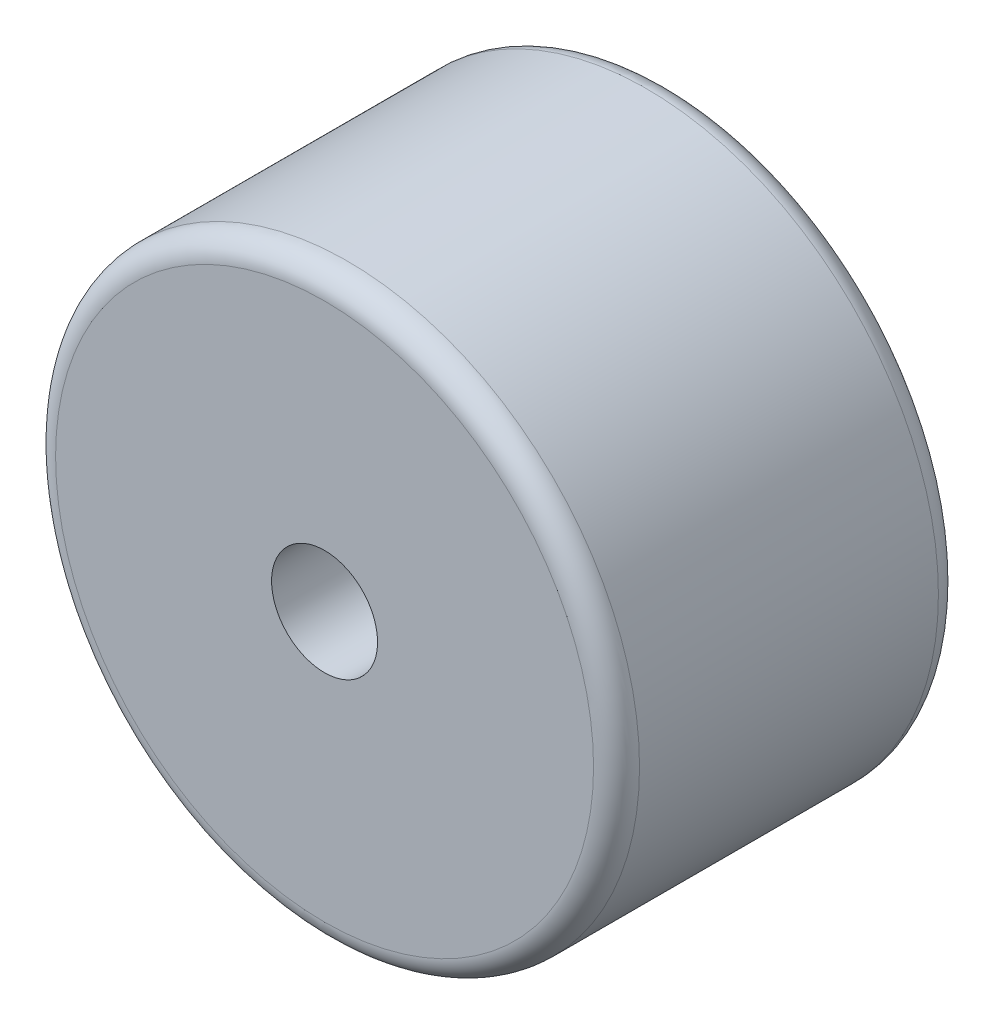
SolidWorks part; units mm, degrees
ref_plane "Front Plane" through (0, 0, 0) normal (0, 0, 1) x (1, 0, 0)
ref_plane "Top Plane" through (0, 0, 0) normal (0, 1, 0) x (1, 0, 0)
ref_plane "Right Plane" through (0, 0, 0) normal (1, 0, 0) x (0, 0, -1)
sketch "body sketch" plane through (0, 0, 0) normal (0, 0, 1) x (1, 0, 0)
  circle A0 centre (0, 0) radius 12.7
  dimension "D1" = 25.4
extrude "wheel body" add sketch "body sketch" along normal mid plane 15 contours A0
sketch "hole sketch" plane through (0, 0, 7.5) normal (0, 0, 1) x (1, 0, 0)
  circle A0 centre (0, 0) radius 2.305
  dimension "D1" = 4.61
fillet "fillet wheel" radius 1 2 edges at (12.7, 0, -7.5) (12.7, 0, 7.5)
extrude "hole shaft" cut sketch "hole sketch" against normal blind 15 contours A0
